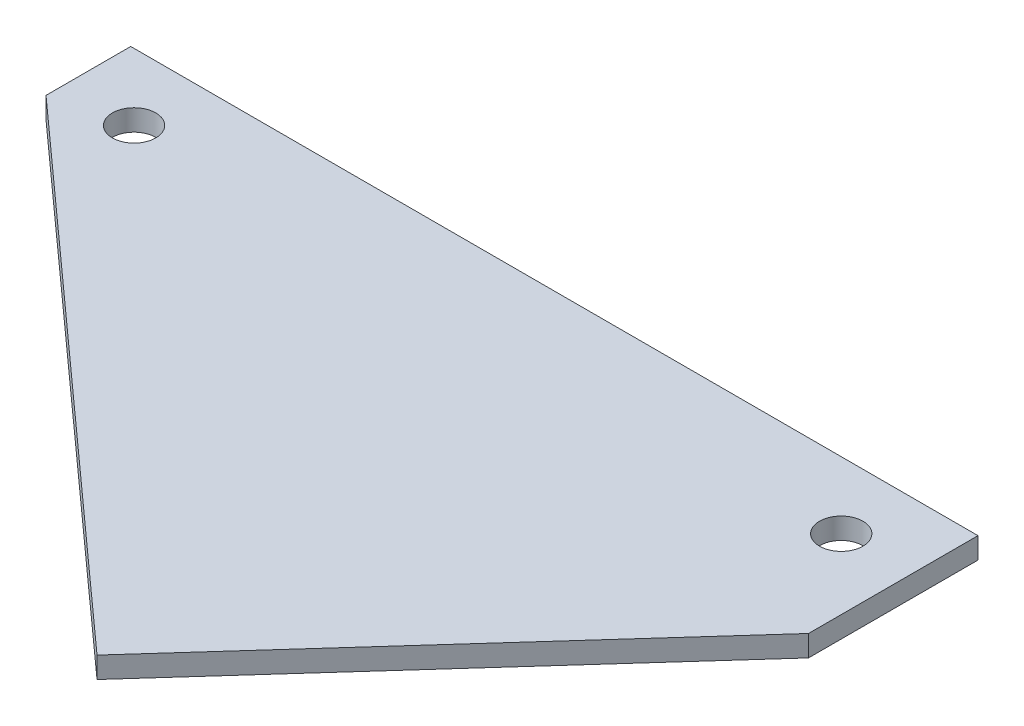
SolidWorks part; units mm, degrees
material "AISI 4130 Steel, annealed at 865C"
ref_plane "X-Y Datum" through (0, 0, 0) normal (0, 0, 1) x (1, 0, 0)
ref_plane "X-Z Datum" through (0, 0, 0) normal (0, 1, 0) x (1, 0, 0)
ref_plane "Y-Z Datum" through (0, 0, 0) normal (1, 0, 0) x (0, 0, -1)
sketch "Sketch1" plane through (0, 0, 0) normal (0, 1, 0) x (1, 0, 0)
  line L0 (0, 38.1) -> (0, -88.9)
  line L1 (-63.5, -88.9) -> (63.5, -88.9)
  line L2 (-63.5, -88.9) -> (-63.5, 38.1)
  line L3 (-63.5, 38.1) -> (63.5, 38.1)
  line L4 (63.5, -88.9) -> (63.5, 38.1)
  point P0 (0, 0)
  dimension "D1" = 127
  dimension "D2" = 38.1
  dimension "D3" = 127
extrude "Boss-Extrude1" add sketch "Sketch1" along normal blind 3.175 contours L3 L4 L1 L2
sketch "Sketch2" plane through (0, 3.175, 0) normal (0, 1, 0) x (1, 0, 0)
  line L0 (-63.5, 25.4) -> (63.5, -88.9)
  line L1 (63.5, 12.7) -> (12.9807, -43.4326)
  line L4 (-63.5, 38.1) -> (-63.5, -88.9)
  line L5 (-63.5, -88.9) -> (63.5, -88.9)
  line L6 (63.5, -88.9) -> (63.5, 38.1)
  line L7 (63.5, 38.1) -> (-63.5, 38.1)
  line L8 (-63.5, 38.1) -> (-63.5, -88.9)
  line L9 (-63.5, -88.9) -> (63.5, -88.9)
  line L10 (63.5, -88.9) -> (63.5, 38.1)
  line L11 (63.5, 38.1) -> (-63.5, 38.1)
  circle A0 centre (53, 28.1) radius 3.25 construction
  circle A1 centre (-53, 28.1) radius 3.25 construction
  circle A2 centre (53, 28.1) radius 3.25
  circle A3 centre (-53, 28.1) radius 3.25
  line M5 (-63.5, 38.1) -> (-63.5, -88.9)
  line M6 (-63.5, -88.9) -> (63.5, -88.9)
  line M7 (63.5, -88.9) -> (63.5, 38.1)
  dimension "D2" = 12.7
  dimension "D3" = 127
  dimension "D4" = 25.4
  dimension "D1" = 0
extrude "Cut-Extrude1" cut sketch "Sketch2" against normal through all contours L0 M5 M6 | A3 | A2 | L1 L0 M7 region at (-21.1667, 3.175, 50.8) region at (46.6602, 3.175, 39.8775) region at (53, 3.175, -28.1) region at (-53, 3.175, -28.1)
